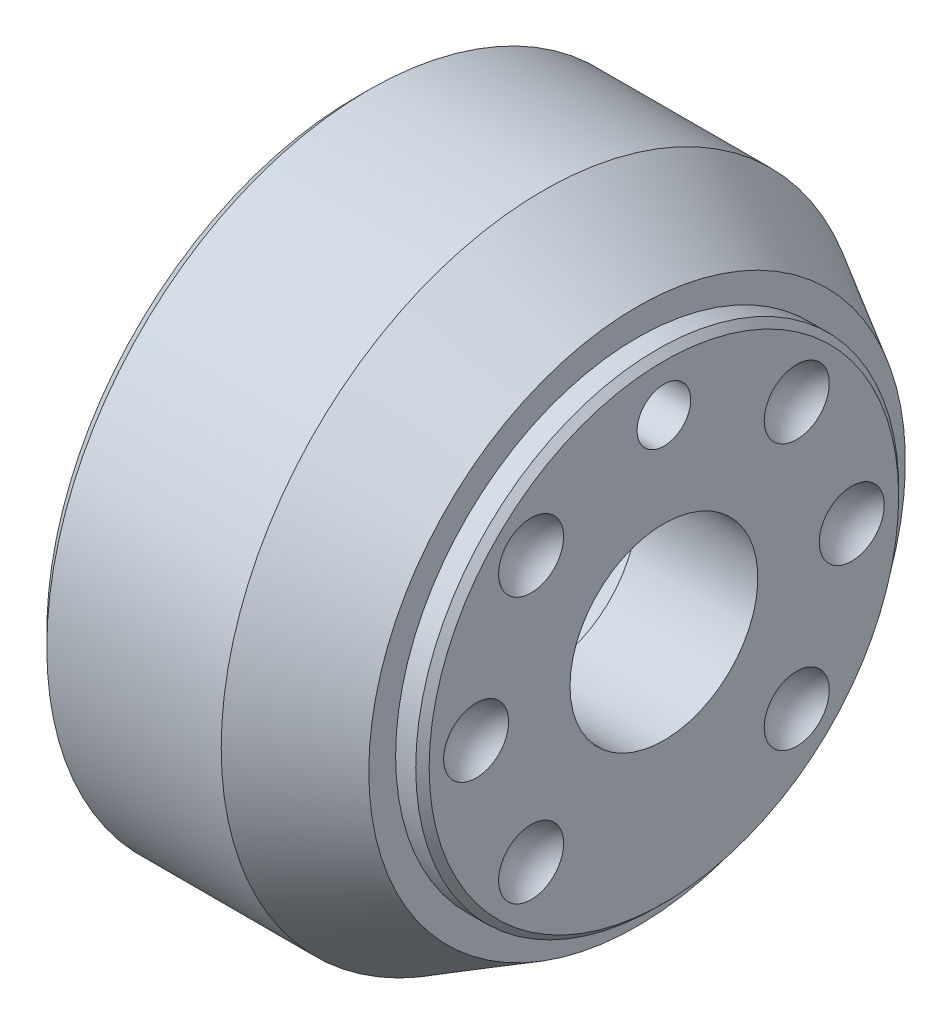
SolidWorks part; units mm, degrees
ref_plane "前视基准面" through (0, 0, 0) normal (0, 0, 1) x (1, 0, 0)
ref_plane "上视基准面" through (0, 0, 0) normal (0, 1, 0) x (1, 0, 0)
ref_plane "右视基准面" through (0, 0, 0) normal (1, 0, 0) x (0, 0, -1)
other "Configuration Table"
sketch "草图1" plane through (0, 0, 0) normal (0, 0, 1) x (1, 0, 0)
  line L0 (-36.9219, 0) -> (36.9219, 0) construction
  line L1 (0, 7) -> (-9, 7)
  line L2 (-9, 7) -> (-9, 9)
  line L3 (-9, 9) -> (-8, 9)
  line L4 (-8, 9) -> (-8, 18)
  line L5 (-8, 18) -> (-23, 18)
  line L6 (-23, 18) -> (-23, 24)
  line L7 (-23, 24) -> (-9, 24)
  line L8 (-9, 24) -> (-2, 20)
  line L9 (-2, 20) -> (-2, 18)
  line L10 (-2, 18) -> (0, 18)
  line L11 (0, 18) -> (0, 7)
  point P5 (0, 0)
  dimension "D1" = 14
  dimension "D2" = 18
  dimension "D3" = 36
  dimension "D4" = 48
  dimension "D5" = 36
  dimension "D6" = 40
  dimension "D7" = 23
  dimension "D8" = 2
  dimension "D9" = 14
  dimension "D10" = 1
  dimension "D11" = 15
revolve "旋转1" add sketch "草图1" angle 360 about L0
sketch "草图2" plane through (0, 0, 0) normal (1, 0, 0) x (0, 0, -1)
  circle A0 centre (0, 0) radius 14 construction
  circle A1 centre (0, 14) radius 2
  dimension "D1" = 4
  dimension "D2" = 28
extrude "切除-拉伸1" cut sketch "草图2" against normal blind 4
sketch "草图3" plane through (0, 0, 0) normal (0, 1, 0) x (1, 0, 0)
  line L0 (0, -18) -> (0, 18) construction
  line L1 (1.4, 16.8) -> (1.4, 11.2) construction
  line L2 (1.4, 16.8) -> (1.4, 11.2)
  arc A0 (1.4, 16.8) -> (1.4, 11.2) centre (1.4, 14) ccw
  dimension "D1" = 5.6
  dimension "D2" = 1.4
  dimension "D3" = 14
revolve "切除-旋转1" cut sketch "草图3" angle 360 about L1
pattern_circular "阵列(圆周)1" count 8 over 360 about axis through (0, 0, 0) along (-1, 0, 0) skipping 2, 6 of "切除-旋转1"
sketch "草图4" plane through (-23, 0, 0) normal (-1, 0, 0) x (0, 0, 1)
  circle A0 centre (0, 0) radius 20.75 construction
  dimension "D1" = 41.5
hole_wizard "M4 螺纹孔1" positions "草图5" profile "草图6" tap size "M4" standard "GB"
sketch "草图5" plane through (-23, 0, 0) normal (-1, 0, 0) x (0, 0, 1)
  circle A0 centre (0, 0) radius 20.75 construction
  point P0 (0, 20.75)
  point P4 (20.75, 0)
  point P6 (-20.75, 0)
  point P8 (0, -20.75)
sketch "草图6" plane through (-23, 20.75, 0) normal (0, 1, 0) x (0, 0, 1)
  line L0 (0, 0) -> (0, 8.9914)
  line L1 (0, 8.9914) -> (1.65, 8)
  line L2 (1.65, 8) -> (1.65, 0.375)
  line L3 (1.65, 0.375) -> (2.025, 0)
  line L5 (2.025, 0) -> (0, 0)
  line L6 (-1.65, 0.375) -> (-2.025, 0) construction
  line L10 (0, 8.9914) -> (-1.65, 8) construction
  line L11 (0, -6.35) -> (0, 107.95) construction
  dimension "螺纹孔钻头直径" = 3.3
  dimension "螺纹孔钻头深度" = 8
  dimension "近端锥形沉头孔直径" = 4.05
  dimension "近端锥形沉头孔角度" = 90
  dimension "导头角度" = 118
cosmetic thread "孔螺蚊线1" parameters "D1"=5, "D2"=4
cosmetic thread "孔螺蚊线2" parameters "D1"=5, "D2"=4
cosmetic thread "孔螺蚊线3" parameters "D1"=5, "D2"=4
cosmetic thread "孔螺蚊线4" parameters "D1"=5, "D2"=4
chamfer "倒角1" distance 1 angle 45 1 edges at (-23, 0, 24)
chamfer "倒角2" distance 0.5 angle 45 1 edges at (0, 0, 18)
